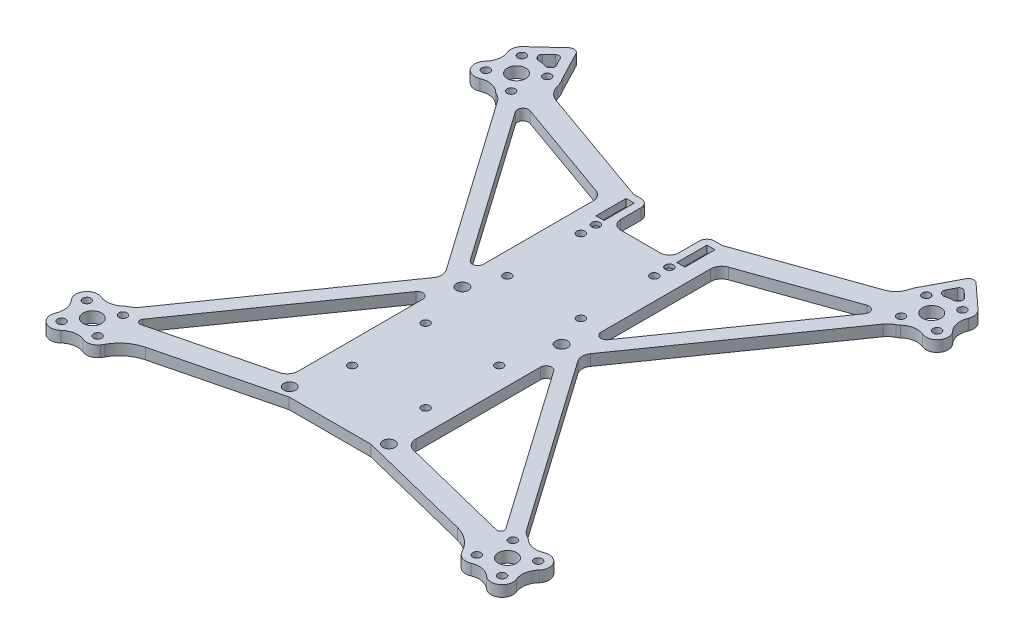
SolidWorks part; units mm, degrees
ref_plane "Front Plane" through (0, 0, 0) normal (0, 0, 1) x (1, 0, 0)
ref_plane "Top Plane" through (0, 0, 0) normal (0, 1, 0) x (1, 0, 0)
ref_plane "Right Plane" through (0, 0, 0) normal (1, 0, 0) x (0, 0, -1)
sketch "Sketch1" plane through (0, 0, 0) normal (0, 1, 0) x (1, 0, 0)
  line L0 (0, 42.225) -> (0, -42.225) construction
  line L1 (16, 42.225) -> (-16, 42.225)
  line L2 (16, 42.225) -> (16, -42.225)
  line L3 (16, -42.225) -> (-16, -42.225)
  line L4 (-16, 42.225) -> (-16, -42.225)
  line L5 (16, 42.225) -> (-16, -42.225) construction
  line L6 (16, -42.225) -> (-16, 42.225) construction
  line L12 (-12.1, 50.425) -> (-12.1, 52.425) construction
  line L17 (-11, 52.425) -> (-11, 42.225) construction
  line L18 (-7.9, 42.225) -> (-14.1, 42.225)
  line L20 (-10, 36) -> (10, 36)
  line L21 (-10, 36) -> (-10, 16)
  line L22 (-10, 16) -> (10, 16)
  line L23 (10, 36) -> (10, 16)
  line L24 (-10, 36) -> (10, 16) construction
  line L25 (-10, 16) -> (10, 36) construction
  line L26 (-14.5, 10.775) -> (14.5, 10.775)
  line L27 (-14.5, 10.775) -> (-14.5, 41.225)
  line L28 (-14.5, 41.225) -> (14.5, 41.225)
  line L29 (14.5, 10.775) -> (14.5, 41.225)
  line L30 (-14.5, 10.775) -> (14.5, 41.225) construction
  line L31 (-14.5, 41.225) -> (14.5, 10.775) construction
  line L32 (-10, -6.225) -> (10, -6.225)
  line L33 (-10, -6.225) -> (-10, -26.225)
  line L34 (-10, -26.225) -> (10, -26.225)
  line L35 (10, -6.225) -> (10, -26.225)
  line L36 (-10, -6.225) -> (10, -26.225) construction
  line L37 (-10, -26.225) -> (10, -6.225) construction
  line L38 (-15.75, -36.225) -> (15.75, -36.225)
  line L39 (-15.75, -36.225) -> (-15.75, 3.775)
  line L40 (-15.75, 3.775) -> (15.75, 3.775)
  line L41 (15.75, -36.225) -> (15.75, 3.775)
  line L42 (-15.75, -36.225) -> (15.75, 3.775) construction
  line L43 (-15.75, 3.775) -> (15.75, -36.225) construction
  line L48 (-7.9, 42.225) -> (-7.9, 52.425)
  line L49 (-7.9, 52.425) -> (-14.1, 52.425)
  line L59 (-14.1, 42.225) -> (-14.1, 52.425)
  line L63 (-12.1, 50.425) -> (-9.9, 50.425)
  line L64 (-12.1, 50.425) -> (-12.1, 42.225)
  line L65 (-12.1, 42.225) -> (-9.9, 42.225)
  line L66 (-9.9, 50.425) -> (-9.9, 42.225)
  line L67 (-12.1, 50.425) -> (-9.9, 42.225) construction
  line L68 (-12.1, 42.225) -> (-9.9, 50.425) construction
  line L69 (-12.1, 50.425) -> (-14.1, 50.425) construction
  line L74 (7.9, 42.225) -> (14.1, 42.225)
  line L75 (14.1, 42.225) -> (14.1, 52.425)
  line L76 (7.9, 52.425) -> (14.1, 52.425)
  line L77 (7.9, 42.225) -> (7.9, 52.425)
  line L78 (12.1, 50.425) -> (9.9, 50.425)
  line L79 (12.1, 50.425) -> (12.1, 42.225)
  line L80 (12.1, 42.225) -> (9.9, 42.225)
  line L81 (9.9, 50.425) -> (9.9, 42.225)
  line L82 (-14.5, 10.775) -> (-14.5, 3.775) construction
  line L83 (-14.5, 7.275) -> (16, 7.275) construction
  line L89 (-13.5, -37.225) -> (-16, -37.225) construction
  line L94 (-14.1, 52.425) -> (-16, 52.425)
  line L95 (-14.1, 52.425) -> (-14.1, 42.225)
  line L96 (-14.1, 42.225) -> (-16, 42.225)
  line L97 (-16, 52.425) -> (-16, 42.225)
  line L98 (14.1, 52.425) -> (16, 52.425)
  line L99 (14.1, 52.425) -> (14.1, 42.225)
  line L100 (14.1, 42.225) -> (16, 42.225)
  line L101 (16, 52.425) -> (16, 42.225)
  circle A3 centre (-10, 36) radius 1.1
  circle A4 centre (10, 36) radius 1.1
  circle A5 centre (10, 16) radius 1.1
  circle A6 centre (-10, 16) radius 1.1
  circle A7 centre (-10, -6.225) radius 1.1
  circle A8 centre (10, -6.225) radius 1.1
  circle A9 centre (10, -26.225) radius 1.1
  circle A10 centre (-10, -26.225) radius 1.1
  circle A37 centre (-13.5, 7.275) radius 2.5
  circle A38 centre (-13.5, 7.275) radius 1.625
  circle A39 centre (13.5, 7.275) radius 1.625
  circle A40 centre (-13.5, -39.725) radius 2.5
  circle A41 centre (-13.5, -39.725) radius 1.625
  circle A42 centre (13.5, -39.725) radius 1.625
  point P0 (0, 0)
  point P8 (0, 0)
  point P16 (0, 26)
  point P26 (0, 26)
  point P31 (0, -16.225)
  point P36 (0, -16.225)
  point P61 (-11, 46.325)
  dimension "D3" = 2
  dimension "D17" = 2.2
  dimension "D22" = 5
  dimension "D23" = 3.25
  dimension "D8" = 32
  dimension "D9" = 22
  dimension "D10" = 20
  dimension "D11" = 29
  dimension "D12" = 30.45
  dimension "D13" = 40
  dimension "D14" = 31.5
  dimension "D15" = 1
  dimension "D16" = 7
  dimension "D18" = 2.2
  dimension "D20" = 8.2
  dimension "D24" = 1
extrude "Base shape" add sketch "Sketch1" along normal blind 2 contours L63 L66 L1 L48 L49 L59 L18 L64 | L81 L78 L79 L1 L75 L76 L77 | L94 L97 L1 L59 | L101 L98 L75 L1 | L1 L4 L3 L2 | A4 | A3 | A7 | A8 | A9 | A10 | A5 | A6 | A39 | A38 | A41 | A42 region at (15.05, 0, -47.325) region at (13.1, 0, -42.3444) region at (-8.9, 0, -42.3444) region at (-15.05, 0, -47.325)
sketch "Sketch2" plane through (0, 0, 0) normal (0, -1, 0) x (1, 0, 0)
  line L0 (-12.1, -42.225) -> (-9.9, -50.425) construction
  line L1 (12.1, -42.225) -> (9.9, -50.425) construction
  line L4 (12.1, -42.225) -> (9.9, -42.225)
  line L5 (12.1, -50.425) -> (12.1, -42.225)
  line L6 (9.9, -50.425) -> (12.1, -50.425)
  line L7 (9.9, -42.225) -> (9.9, -50.425)
  line L8 (12.1, -42.225) -> (9.9, -42.225)
  line L9 (12.1, -50.425) -> (12.1, -42.225)
  line L10 (9.9, -50.425) -> (12.1, -50.425)
  line L11 (9.9, -42.225) -> (9.9, -50.425)
  line L12 (-9.9, -42.225) -> (-12.1, -42.225)
  line L13 (-9.9, -50.425) -> (-9.9, -42.225)
  line L14 (-12.1, -50.425) -> (-9.9, -50.425)
  line L15 (-12.1, -42.225) -> (-12.1, -50.425)
  line L16 (-9.9, -42.225) -> (-12.1, -42.225)
  line L17 (-9.9, -50.425) -> (-9.9, -42.225)
  line L18 (-12.1, -50.425) -> (-9.9, -50.425)
  line L19 (-12.1, -42.225) -> (-12.1, -50.425)
  circle A0 centre (-11, -46.325) radius 1.1
  circle A1 centre (11, -46.325) radius 1.1
  dimension "D1" = 0
  dimension "D2" = 0
extrude "Camera mount pockets" add sketch "Sketch2" against normal offset from surface (1 mm away) 1 contours A0 L19 | A0 L17 | A1 L9 | A1 L11 region at (11, 0, -43.8523) region at (11, 0, -48.7977) region at (-11, 0, -43.8523) region at (-11, 0, -48.7977) up to face at (11, 2, -46.325)
fillet "Main fillets" radius 2.5 6 edges at (7.9, 1, -42.225) (-7.9, 1, -42.225) (-16, 1, -52.425) (16, 1, -52.425) (-16, 1, 42.225) (16, 1, 42.225)
fillet "Inner camera mount fillets" radius 2.1 2 edges at (-7.9, 1, -52.425) (7.9, 1, -52.425)
sketch "Sketch3" plane through (0, 2, 0) normal (0, 1, 0) x (1, 0, 0)
  line L6 (12.1, 42.225) -> (12.1, 50.425)
  line L7 (9.9, 42.225) -> (12.1, 42.225)
  line L8 (-10, 52.425) -> (-13.5, 52.425)
  line L9 (-16, 49.925) -> (-16, -39.725)
  line L10 (-13.5, -42.225) -> (13.5, -42.225)
  line L11 (16, -39.725) -> (16, 49.925)
  line L12 (13.5, 52.425) -> (10, 52.425)
  line L13 (7.9, 50.325) -> (7.9, 44.725)
  line L14 (5.4, 42.225) -> (-5.4, 42.225)
  line L15 (-7.9, 44.725) -> (-7.9, 50.325)
  line L16 (-10, 52.425) -> (-13.5, 52.425)
  line L17 (-16, 49.925) -> (-16, -39.725)
  line L18 (-13.5, -42.225) -> (13.5, -42.225)
  line L19 (16, -39.725) -> (16, 49.925)
  line L20 (13.5, 52.425) -> (10, 52.425)
  line L21 (7.9, 50.325) -> (7.9, 44.725)
  line L22 (5.4, 42.225) -> (-5.4, 42.225)
  line L23 (-7.9, 44.725) -> (-7.9, 50.325)
  line L24 (9.9, 50.425) -> (9.9, 42.225)
  line L25 (12.1, 50.425) -> (9.9, 50.425)
  line L26 (12.1, 42.225) -> (12.1, 50.425)
  line L27 (9.9, 42.225) -> (12.1, 42.225)
  line L28 (9.9, 50.425) -> (9.9, 42.225)
  line L29 (12.1, 50.425) -> (9.9, 50.425)
  line L30 (-9.9, 42.225) -> (-9.9, 50.425)
  line L31 (-12.1, 42.225) -> (-9.9, 42.225)
  line L32 (-12.1, 50.425) -> (-12.1, 42.225)
  line L33 (-9.9, 50.425) -> (-12.1, 50.425)
  line L34 (-9.9, 42.225) -> (-9.9, 50.425)
  line L35 (-12.1, 42.225) -> (-9.9, 42.225)
  line L36 (-12.1, 50.425) -> (-12.1, 42.225)
  line L37 (-9.9, 50.425) -> (-12.1, 50.425)
  circle A0 centre (13.5, -39.725) radius 1.625 construction
  circle A1 centre (-13.5, -39.725) radius 1.625 construction
  circle A2 centre (-13.5, 7.275) radius 1.625 construction
  circle A3 centre (-10, -6.225) radius 1.1 construction
  circle A4 centre (-10, -26.225) radius 1.1 construction
  circle A5 centre (10, -26.225) radius 1.1 construction
  circle A6 centre (10, -6.225) radius 1.1 construction
  circle A7 centre (13.5, 7.275) radius 1.625 construction
  arc A8 (-13.5, 52.425) -> (-16, 49.925) centre (-13.5, 49.925) ccw
  arc A9 (-16, -39.725) -> (-13.5, -42.225) centre (-13.5, -39.725) ccw
  arc A10 (13.5, -42.225) -> (16, -39.725) centre (13.5, -39.725) ccw
  arc A11 (16, 49.925) -> (13.5, 52.425) centre (13.5, 49.925) ccw
  arc A12 (-7.9, 50.325) -> (-10, 52.425) centre (-10, 50.325) ccw
  arc A13 (5.4, 42.225) -> (7.9, 44.725) centre (5.4, 44.725) ccw
  arc A14 (-7.9, 44.725) -> (-5.4, 42.225) centre (-5.4, 44.725) ccw
  arc A15 (-7.9, 50.325) -> (-10, 52.425) centre (-10, 50.325) ccw
  arc A16 (-13.5, 52.425) -> (-16, 49.925) centre (-13.5, 49.925) ccw
  arc A17 (-16, -39.725) -> (-13.5, -42.225) centre (-13.5, -39.725) ccw
  arc A18 (13.5, -42.225) -> (16, -39.725) centre (13.5, -39.725) ccw
  arc A19 (16, 49.925) -> (13.5, 52.425) centre (13.5, 49.925) ccw
  arc A21 (5.4, 42.225) -> (7.9, 44.725) centre (5.4, 44.725) ccw
  arc A22 (-7.9, 44.725) -> (-5.4, 42.225) centre (-5.4, 44.725) ccw
  circle A24 centre (-10, 16) radius 1.1 construction
  circle A25 centre (-10, 36) radius 1.1 construction
  circle A26 centre (10, 36) radius 1.1 construction
  circle A27 centre (10, 16) radius 1.1 construction
  circle A28 centre (10, 16) radius 1.1
  circle A29 centre (10, 36) radius 1.1
  circle A30 centre (-10, 36) radius 1.1
  circle A31 centre (-10, 16) radius 1.1
  circle A32 centre (13.5, 7.275) radius 1.625
  circle A33 centre (10, -6.225) radius 1.1
  circle A34 centre (10, -26.225) radius 1.1
  circle A35 centre (-10, -26.225) radius 1.1
  circle A36 centre (-10, -6.225) radius 1.1
  circle A37 centre (13.5, -39.725) radius 1.625
  circle A38 centre (-13.5, -39.725) radius 1.625
  circle A39 centre (-13.5, 7.275) radius 1.625
  arc A48 (10, 52.425) -> (7.9, 50.325) centre (10, 50.325) ccw
  arc A49 (10, 52.425) -> (7.9, 50.325) centre (10, 50.325) ccw
  dimension "D1" = 0
  dimension "D2" = 0
  dimension "D3" = 0
extrude "Thicker base" add sketch "Sketch3" along normal blind 1
sketch "Sketch4" plane through (0, 0, 0) normal (0, -1, 0) x (1, 0, 0)
  line L0 (0, 13.9568) -> (0, -8.6953) construction
  line L1 (-14.1, -38.5) -> (-5.9, -38.5)
  line L2 (-14.1, -38.5) -> (-14.1, -41.7)
  line L3 (-14.1, -41.7) -> (-5.9, -41.7)
  line L4 (-5.9, -38.5) -> (-5.9, -41.7)
  line L5 (-10, -38.5) -> (-10, -41.7) construction
  line L7 (14.1, -38.5) -> (5.9, -38.5)
  line L8 (14.1, -38.5) -> (14.1, -41.7)
  line L9 (14.1, -41.7) -> (5.9, -41.7)
  line L10 (5.9, -38.5) -> (5.9, -41.7)
  line L11 (-14.1, -38.5) -> (-10.9, -41.7) construction
  line L12 (-14.1, -40.1) -> (-5.9, -40.1) construction
  circle A0 centre (-10, -36) radius 2
  circle A1 centre (-13.3929, -39.2071) radius 1
  circle A2 centre (-13.3929, -40.9929) radius 1
  circle A3 centre (-6.6071, -39.2071) radius 1
  circle A4 centre (-6.6071, -40.9929) radius 1
  circle A5 centre (6.6071, -40.9929) radius 1
  circle A6 centre (6.6071, -39.2071) radius 1
  circle A7 centre (13.3929, -39.2071) radius 1
  circle A8 centre (13.3929, -40.9929) radius 1
  point P9 (-10, -38)
  dimension "D5" = 4
  dimension "D7" = 2
  dimension "D1" = 8.2
  dimension "D2" = 3.2
  dimension "D3" = 10
  dimension "D4" = 0.5
  dimension "D6" = 45
extrude "Battery holder pockets" cut sketch "Sketch4" against normal offset from surface (2 mm away) 1 contours A2 L2 | A2 L3 | L2 A1 | L1 A1 | A3 L4 | A3 L1 | L4 A4 | L3 A4 | A5 L9 | A5 L10 | L10 A6 | L7 A6 | A7 L7 | A7 L8 | L8 A8 | L9 A8 | L3 L4 L1 L2 | L9 L10 L7 L8 region at (-13.3929, 0, -38.3812) region at (-14.2188, 0, -39.2071) region at (-6.6071, 0, -38.3812) region at (-14.2188, 0, -40.9929) region at (-5.7812, 0, -39.2071) region at (-13.3929, 0, -41.8188) region at (-6.6071, 0, -41.8188) region at (-5.7812, 0, -40.9929) region at (14.2188, 0, -39.2071) region at (13.3929, 0, -38.3812) region at (6.6071, 0, -38.3812) region at (14.2188, 0, -40.9929) region at (5.7812, 0, -39.2071) region at (13.3929, 0, -41.8188) region at (6.6071, 0, -41.8188) region at (5.7812, 0, -40.9929) up to face at (-13.5, 3, 41.35)
sketch "Sketch5" plane through (0, 2, 0) normal (0, -1, 0) x (1, 0, 0)
  line L0 (-10, -38.5) -> (-10, -41.7) construction
  line L1 (-12.6858, -38.5) -> (-7.3142, -38.5) construction
  line L2 (-12.6858, -41.7) -> (-7.3142, -41.7) construction
  line L3 (0, 5.9884) -> (0, -5.6723) construction
  circle A0 centre (-10, -40.1) radius 1.1
  circle A1 centre (10, -40.1) radius 1.1
  dimension "D1" = 2.2
extrude "Battery holder holes" cut sketch "Sketch5" against normal up to next
sketch "Sketch6" [suppressed] plane through (0, 0, 0) normal (0, -1, 0) x (1, 0, 0)
  line L0 (0, -5.1) -> (0, 9.653) construction
  line L8 (-13.5, -7.275) -> (13.5, -7.275) construction
  line L10 (-16, -25.775) -> (16, -25.775) construction
  line L11 (-16, -49.925) -> (-16, 39.725) construction
  line L12 (16, -49.925) -> (16, 39.725) construction
  line L13 (17.5, -34.275) -> (19, -34.275)
  line L14 (16, -37.275) -> (19, -37.275)
  line L15 (16, -37.275) -> (16, -14.275)
  line L16 (16, -14.275) -> (19, -14.275)
  line L17 (19, -37.275) -> (19, -14.275)
  line L18 (16, -37.275) -> (19, -14.275) construction
  line L19 (16, -14.275) -> (19, -37.275) construction
  line L20 (16, -35.775) -> (17.5, -35.775)
  line L21 (16, -35.775) -> (16, -15.775)
  line L22 (16, -15.775) -> (17.5, -15.775)
  line L23 (17.5, -35.775) -> (17.5, -15.775)
  line L24 (16, -35.775) -> (17.5, -15.775) construction
  line L25 (16, -15.775) -> (17.5, -35.775) construction
  line L26 (17.5, -17.275) -> (19, -17.275)
  line L27 (-17.5, -34.275) -> (-19, -34.275)
  line L28 (-17.5, -17.275) -> (-19, -17.275)
  line L29 (-16, -35.775) -> (-16, -15.775)
  line L30 (-16, -35.775) -> (-17.5, -35.775)
  line L31 (-17.5, -35.775) -> (-17.5, -15.775)
  line L32 (-16, -15.775) -> (-17.5, -15.775)
  line L33 (-16, -37.275) -> (-16, -14.275)
  line L34 (-16, -37.275) -> (-19, -37.275)
  line L35 (-19, -37.275) -> (-19, -14.275)
  line L36 (-16, -14.275) -> (-19, -14.275)
  line L37 (16, 22.725) -> (19, 22.725)
  line L38 (16, 22.725) -> (16, -0.275)
  line L39 (16, -0.275) -> (19, -0.275)
  line L40 (19, 22.725) -> (19, -0.275)
  line L41 (16, 21.225) -> (17.5, 21.225)
  line L42 (16, 21.225) -> (16, 1.225)
  line L43 (16, 1.225) -> (17.5, 1.225)
  line L44 (17.5, 21.225) -> (17.5, 1.225)
  line L45 (17.5, 2.725) -> (19, 2.725)
  line L46 (17.5, 19.725) -> (19, 19.725)
  line L47 (-17.5, 19.725) -> (-19, 19.725)
  line L48 (-17.5, 2.725) -> (-19, 2.725)
  line L49 (-16, 21.225) -> (-16, 1.225)
  line L50 (-16, 21.225) -> (-17.5, 21.225)
  line L51 (-17.5, 21.225) -> (-17.5, 1.225)
  line L52 (-16, 1.225) -> (-17.5, 1.225)
  line L53 (-16, 22.725) -> (-16, -0.275)
  line L54 (-16, 22.725) -> (-19, 22.725)
  line L55 (-19, 22.725) -> (-19, -0.275)
  line L56 (-16, -0.275) -> (-19, -0.275)
  point P19 (17.5, -25.775)
  point P25 (16.75, -25.775)
  line M18 (16, -49.925) -> (16, 39.725)
  line M22 (-16, 39.725) -> (-16, -49.925)
  dimension "D1" = 14
  dimension "D4" = 23
  dimension "D5" = 3
  dimension "D6" = 1.5
  dimension "D7" = 20
  dimension "D8" = 1.5
extrude "Strap holders" [suppressed] add sketch "Sketch6" against normal up to surface (2 mm away) contours L23 L20 L14 L17 L13 M18 | L23 L26 L17 L16 L22 M18 | L45 L44 L43 L39 L40 M18 | L44 L46 L40 L37 L38 L41 | L54 L55 L47 L51 L50 M22 | L56 L52 L51 L48 L55 M22 | L36 L35 L28 L31 L32 M22 | L35 L34 L30 L31 L27 M22 up to face at (-10, 2, -41.2)
fillet "Strap holder fillets" [suppressed] radius 0.75
sketch "Sketch7" plane through (0, 3, 0) normal (0, 1, 0) x (1, 0, 0)
  line L0 (-56.5, 65) -> (-16, 50.6258) construction
  line L1 (56.5, -65) -> (-56.5, -65)
  line L2 (56.5, -65) -> (56.5, 65)
  line L3 (56.5, 65) -> (-56.5, 65)
  line L4 (-56.5, -65) -> (-56.5, 65)
  line L5 (56.5, -65) -> (-56.5, 65) construction
  line L6 (56.5, 65) -> (-56.5, -65) construction
  line L7 (-16, 49.925) -> (-16, -39.725) construction
  line L8 (-57.5034, 62.1728) -> (-17.0034, 47.7986)
  line L9 (-47.5, 64.9891) -> (-12.1, 52.425)
  line L10 (-55.4966, 67.8272) -> (-14.9966, 53.453) construction
  line L11 (-13.5, 7.275) -> (13.5, 7.275) construction
  line L12 (-63.8675, 59.8309) -> (-49.1325, 70.1691) construction
  line L13 (-56.5, 65) -> (-16, 7.275) construction
  line L14 (-58.1372, 63.8513) -> (-17.6372, 6.1263)
  line L15 (-54.8628, 66.1487) -> (-14.3628, 8.4237)
  line L16 (-17.6372, 6.1263) -> (-16, 3.7928)
  line L17 (-56.5, 65) -> (-59.9461, 69.9117) construction
  line L18 (-56.5, 74) -> (-56.5, 56) construction
  line L19 (-59.9461, 69.9117) -> (-51.5883, 68.4461) construction
  line L20 (-55.7672, 69.1789) -> (-54.3854, 77.0586) construction
  line L21 (-55.4003, 78.1631) -> (-61.8454, 72.2407)
  line L22 (-53.0552, 77.7519) -> (-49.0099, 69.9898)
  line L23 (-54.6445, 75.5812) -> (-58.1773, 72.3348)
  line L24 (-54.6445, 75.5812) -> (-52.427, 71.3264)
  line L25 (-58.1372, -49.3013) -> (-17.6372, 8.4237)
  line L26 (-54.8628, -51.5987) -> (-14.3628, 6.1263)
  line L27 (-56.5, -50.45) -> (-13.5, -39.725) construction
  line L28 (-47.5409, -51.3073) -> (-11.1269, -42.225)
  line L29 (-57.226, -47.5392) -> (-16, -37.2566)
  line L30 (-55.774, -53.3608) -> (-15.1925, -43.2391) construction
  line L31 (-56.5, -50.45) -> (-15.9185, -40.3282) construction
  line L32 (-13.5, -42.225) -> (13.5, -42.225) construction
  line L33 (-57.226, -47.5392) -> (-16.6446, -37.4174) construction
  line L34 (-17.0034, 47.7986) -> (-16, 47.4425)
  line L35 (-12.1, 50.425) -> (-12.1, 52.425) construction
  line L36 (-10, 52.425) -> (-13.5, 52.425) construction
  circle A0 centre (-56.5, 65) radius 38.1
  circle A1 centre (-56.5, 65) radius 9
  circle A2 centre (-56.5, 65) radius 6
  circle A3 centre (-51.5883, 68.4461) radius 1.1
  circle A4 centre (-61.4117, 61.5539) radius 1.1
  circle A5 centre (-59.9461, 69.9117) radius 1.1
  circle A6 centre (-53.0539, 60.0883) radius 1.1
  circle A7 centre (-59.9461, 69.9117) radius 3
  circle A8 centre (-51.5883, 68.4461) radius 3
  circle A9 centre (-61.4117, 61.5539) radius 3
  circle A10 centre (-53.0539, 60.0883) radius 3
  circle A12 centre (-56.5, 65) radius 2.5
  circle A13 centre (-54.3854, 77.0586) radius 1.5
  circle A14 centre (-67.2007, 66.8765) radius 4.864
  circle A15 centre (-58.3765, 54.2993) radius 4.864
  circle A16 centre (-43.1095, 68.592) radius 4.864
  circle A17 centre (-56.4687, 53.0044) radius 4.864
  circle A18 centre (-46.3458, 56.6211) radius 1.5
  circle A20 centre (-56.5, -50.45) radius 6
  circle A21 centre (-53.0539, -45.5383) radius 1.1
  circle A22 centre (-61.4117, -47.0039) radius 1.1
  circle A23 centre (-59.9461, -55.3617) radius 1.1
  circle A24 centre (-51.5883, -53.8961) radius 1.1
  circle A25 centre (-51.5883, -53.8961) radius 3
  circle A26 centre (-53.0539, -45.5383) radius 3
  circle A27 centre (-56.5, -50.45) radius 2.5
  circle A28 centre (-59.9461, -55.3617) radius 3
  circle A29 centre (-67.2007, -52.3265) radius 4.864
  circle A30 centre (-61.4117, -47.0039) radius 3
  circle A31 centre (-58.3765, -39.7493) radius 4.864
  circle A32 centre (-56.4687, -38.4544) radius 4.864
  circle A34 centre (-56.5, -50.45) radius 9
  circle A35 centre (-54.6235, -61.1507) radius 4.864
  circle A38 centre (-40.0323, -59.55) radius 9.8148
  circle A39 centre (-48.58, -44.3643) radius 0.9882
  point P0 (0, 0)
  point P36 (-53.0539, 60.0883)
  point P54 (-54.6445, 75.5812)
  point P111 (0, 0)
  point P112 (-11.9536, 52.425)
  point P115 (0, 0)
  point P116 (0, 0)
  arc M21 (-7.9, 50.325) -> (-10, 52.425) centre (-10, 50.325) ccw
  line M22 (-10, 52.425) -> (-13.5, 52.425)
  arc M23 (-13.5, 52.425) -> (-16, 49.925) centre (-13.5, 49.925) ccw
  line M24 (-16, 49.925) -> (-16, -39.725)
  arc M25 (-16, -39.725) -> (-13.5, -42.225) centre (-13.5, -39.725) ccw
  line M26 (-13.5, -42.225) -> (13.5, -42.225)
  dimension "D3" = 76.2
  dimension "D4" = 12
  dimension "D5" = 3
  dimension "D10" = 2.2
  dimension "D11" = 5
  dimension "D12" = 3
  dimension "D16" = 3
  dimension "D1" = 113
  dimension "D2" = 130
  dimension "D13" = 8
  dimension "D6" = 3
  dimension "D7" = 3
  dimension "D8" = 2
  dimension "D9" = 2
  dimension "D14" = 3
  dimension "D15" = 3
extrude "Arms" add sketch "Sketch7" against normal up to surface (3 mm away) contours A0 L8 L34 L9 M24 M23 M22 M21 | A1 L8 A0 L9 L3 | A10 L8 A1 L3 A2 | A16 L3 L9 | A8 A2 L3 A1 | A2 A8 A3 | A2 A8 A3 | A12 L3 A2 A8 A7 A9 L4 L14 | A12 L15 A10 A2 L3 | A12 L4 L8 A10 L15 | A12 L14 L8 L4 | A10 L8 L4 L14 | A10 L14 L4 A2 | L8 L14 L4 | A14 A9 A2 | A14 A2 A7 | A15 A2 A9 | A15 A10 A2 L4 | A10 L15 A1 L8 | A10 A1 L15 | A17 A1 L14 A10 | A10 L14 A1 | A17 L14 A1 | A1 L14 A0 L15 | A8 A1 L24 | A13 L24 A1 L22 | A13 | A13 L21 A1 L23 | A7 L23 A1 | A0 L14 L16 L15 M24 | L25 A34 L26 L16 L14 | L29 A34 L28 M26 M25 M24 | A39 L26 A34 | A39 A34 L29 | A34 L25 A26 | A34 A32 A26 L25 | A32 A34 L25 | A26 A31 L4 A20 | L4 A31 A20 | L25 A26 A20 L4 | A20 A30 A28 L4 A27 L25 | A20 A31 A30 | A20 A30 A29 | A20 A29 A28 | A35 L4 A20 A28 | A35 A25 A20 | L26 A27 L4 A20 A25 A26 | A35 A20 L4 | L4 A27 L26 A26 L29 | L29 A26 L25 L4 | L25 L29 L4 | L25 A27 L4 L29 | A38 L28 A34 | A34 L29 A26 A20 A25 | A34 L26 A26 L29 | A34 A26 L26 | A15 L4 A2 | A16 A1 L3 | A18 L8 A1 L15 | A7 | A5 | A9 | A4 | A10 | A6 | A26 | A21 | A30 | A22 | A28 | A23 | A25 | A24 region at (-46.5345, 3, 51.7773) region at (-31.601, 3, 44.2659) region at (-34.4052, 3, -57.1582) region at (-17.9417, 3, -51.3895) region at (-49.06, 3, 49.4225) region at (-46.3969, 3, -64.725) region at (-47.2035, 3, -65.5671) region at (-25.3378, 3, -20.4822) region at (-43.0007, 3, -45.7594) region at (-57.0277, 3, 56.7462) region at (-53.997, 3, 56.1976) region at (-49.2559, 3, -62.7197) region at (-48.6879, 3, -66.3017) region at (-52.9817, 3, -56.4386) region at (-34.3035, 3, 18.799) region at (-48.2643, 3, -58.0794) region at (-56.2418, 3, 56.5049) region at (-62.2476, 3, 52.953) region at (-58.9892, 3, 49.8261) region at (-54.6814, 3, 56.0574) region at (-48.9292, 3, 45.3385) region at (-49.6784, 3, 45.1697) region at (-51.9666, 3, -64.0194) region at (-52.25, 3, -65.1697) region at (-52.2635, 3, -74.178) region at (-49.8439, 3, -59.2851) region at (-52.9817, 3, 41.8886) region at (-53.5081, 3, -56.9644) region at (-52.7431, 3, -57.0001) region at (-49.6265, 3, 44.3971) region at (-52.8596, 3, -67.5541) region at (-50.584, 3, -69.1507) region at (-54.3854, 3, -77.0586) region at (-51.8863, 3, -72.1153) region at (-50.2558, 3, -58.7452) region at (-52.7431, 3, 42.4501) region at (-53.5081, 3, 42.4144) region at (-59.003, 3, 44.7024) region at (-59.003, 3, -59.2524) region at (-62.7563, 3, 50.052) region at (-50.2558, 3, 44.1952) region at (-56.7733, 3, -62.2567) region at (-54.61, 3, -63.0216) region at (-57.3608, 3, -75.0719) region at (-55.9723, 3, 44.1538) region at (-56.7582, 3, 44.3951) region at (-56.7582, 3, -58.9451) region at (-55.9723, 3, -58.7038) region at (-62.7563, 3, -64.602) region at (-56.7834, 3, 47.7337) region at (-54.5593, 3, 48.5183) region at (-56.5931, 3, -61.7501) region at (-56.1129, 3, -61.3788) region at (-58.4174, 3, -73.2606) region at (-56.2641, 3, 45.519) region at (-56.2641, 3, -60.069) region at (-62.2476, 3, -67.503) region at (-56.6107, 3, 47.2556) region at (-56.0931, 3, 46.9042) up to face at (10, 0, -40.1)
fillet "Motor protector fillets" radius 1 5 edges at (-52.427, 1.5, -71.3264) (-53.8706, 1.5, -70.3932) (-57.1374, 1.5, -70.966) (-58.1773, 1.5, -72.3348) (-54.6445, 1.5, -75.5812)
mirror "Arms mirror" about plane through (0, 0, 0) normal (1, 0, 0) of "Arms", "Motor protector fillets"
fillet "Arm fillets outer" radius 3 6 edges at (-16, 1.5, 37.2566) (-16, 1.5, -47.4425) (-18.4432, 1.5, -7.275) (16, 1.5, 37.2566) (18.4432, 1.5, -7.275) (16, 1.5, -47.4425)
fillet "Arm fillets inner" radius 1.5 4 edges at (-16, 1.5, -10.7572) (-16, 1.5, -3.7928) (16, 1.5, -3.7928) (16, 1.5, -10.7572)
